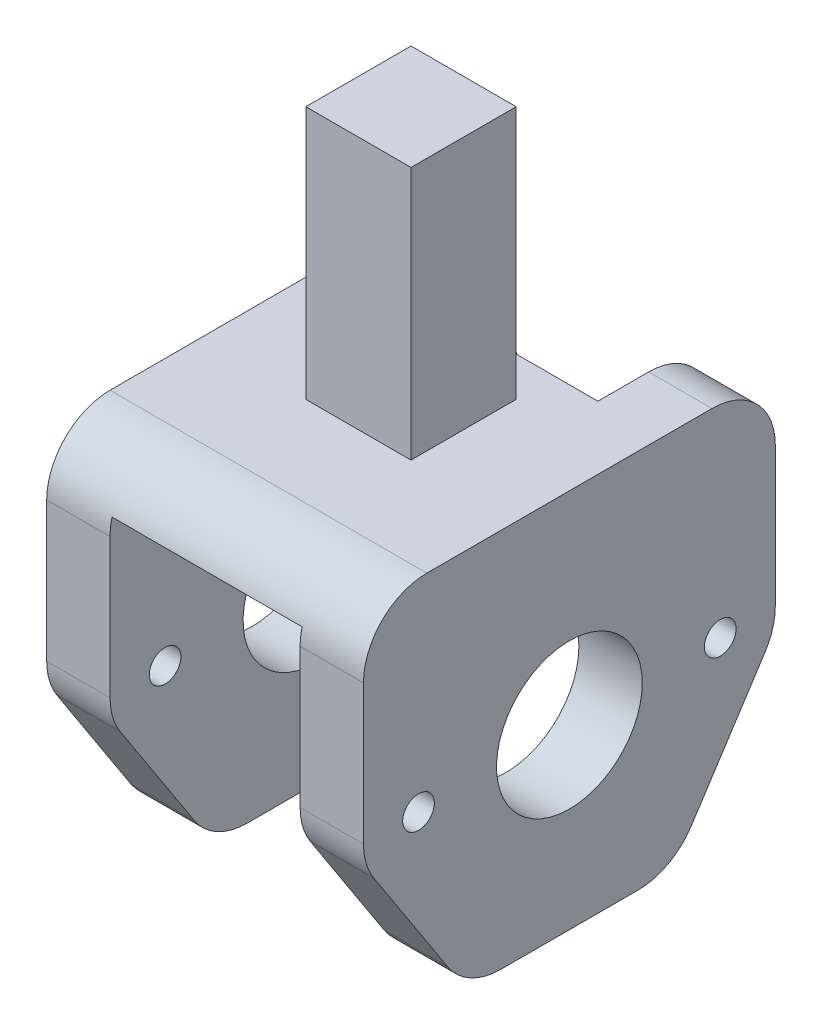
SolidWorks part; units mm, degrees
material "Nylon - impressão"
ref_plane "Plano frontal" through (0, 0, 0) normal (0, 0, 1) x (1, 0, 0)
ref_plane "Plano superior" through (0, 0, 0) normal (0, 1, 0) x (1, 0, 0)
ref_plane "Plano direito" through (0, 0, 0) normal (1, 0, 0) x (0, 0, -1)
sketch "Esboço1" plane through (0, 0, 0) normal (0, 1, 0) x (1, 0, 0)
  line L1 (-8.3, -8.3) -> (8.3, -8.3)
  line L2 (-8.3, -8.3) -> (-8.3, 8.3)
  line L3 (-8.3, 8.3) -> (8.3, 8.3)
  line L4 (8.3, -8.3) -> (8.3, 8.3)
  line L5 (-8.3, -8.3) -> (8.3, 8.3) construction
  line L6 (-8.3, 8.3) -> (8.3, -8.3) construction
  point P0 (0, 0)
  dimension "D1" = 16.6
extrude "Ressalto-extrusão1" add sketch "Esboço1" along normal blind 40
sketch "Esboço2" plane through (0, 0, 0) normal (0, -1, 0) x (1, 0, 0)
  line L1 (-25, -32.5) -> (25, -32.5)
  line L2 (-25, -32.5) -> (-25, 32.5)
  line L3 (-25, 32.5) -> (25, 32.5)
  line L4 (25, -32.5) -> (25, 32.5)
  line L5 (-25, -32.5) -> (25, 32.5) construction
  line L6 (-25, 32.5) -> (25, -32.5) construction
  point P0 (0, 0)
  dimension "D1" = 65
  dimension "D2" = 50
extrude "Ressalto-extrusão2" add sketch "Esboço2" along normal blind 60
sketch "Esboço3" plane through (0, 0, 32.5) normal (0, 0, 1) x (1, 0, 0)
  line L0 (25, -60) -> (-25, -60) construction
  line L1 (-15, -60) -> (15, -60)
  line L2 (-15, -60) -> (-15, -7.5)
  line L3 (-15, -7.5) -> (15, -7.5)
  line L4 (15, -60) -> (15, -7.5)
  line L5 (-25, -60) -> (-25, 0) construction
  line L6 (25, 0) -> (-25, 0) construction
  line L7 (25, -60) -> (25, 0) construction
  dimension "D1" = 10
  dimension "D2" = 7.5
  dimension "D3" = 10
extrude "Corte-extrusão1" cut sketch "Esboço3" against normal through all
sketch "Esboço4" plane through (25, 0, 0) normal (1, 0, 0) x (0, 0, -1)
  line L0 (32.5, -60) -> (-32.5, -60) construction
  line L1 (32.5, -60) -> (32.5, 0) construction
  circle A3 centre (0, -32) radius 11.5
  circle A10 centre (-23.8125, -32) radius 2.5
  circle A13 centre (23.8125, -32) radius 2.5
  circle A16 centre (0, -32) radius 23.8125 construction
  arc A17 (-9.4071, -11.4434) -> (-11.8406, -13.8769) centre (-11.9062, -11.3778) ccw [skipped]
  arc A18 (11.8464, -13.8771) -> (13.5071, -13.298) centre (11.9063, -11.3778) ccw [skipped]
  arc A20 (-11.8406, -55.1214) -> (-14.4054, -52.5566) centre (-11.9062, -52.6222) ccw [skipped]
  arc A21 (11.8345, -55.1212) -> (10.2346, -54.4811) centre (11.9063, -52.6222) ccw [skipped]
  point P9 (23.8125, -32)
  point P21 (0, -32)
  point P22 (0, -32)
  dimension "D2" = 47.625
  dimension "D4" = 5
  dimension "D5" = 23
  dimension "D1" = 28
  dimension "D3" = 32.5
  dimension "D6" = 6
extrude "Corte-extrusão2" cut sketch "Esboço4" against normal through all
sketch "Esboço5" plane through (-25, 0, 0) normal (-1, 0, 0) x (0, 0, 1)
  line L0 (0, 0) -> (0, -9.2798) construction
  line L1 (32.5, 0) -> (-32.5, 0) construction
  line L3 (-14.5, -11) -> (-14.5, 0)
  line L4 (-14.5, 0) -> (-32.5, 0)
  line L5 (-32.5, 0) -> (-32.5, -11)
  line L6 (-32.5, -60) -> (-32.5, 0) construction
  line L7 (-32.5, -11) -> (-14.5, -11)
  dimension "D1" = 18
  dimension "D2" = 11
extrude "Corte-extrusão3" cut sketch "Esboço5" against normal blind 40
chamfer "Chanfro1" distance 25 angle 33 4 edges at (-20, -60, -32.5) (-20, -60, 32.5) (20, -60, 32.5) (20, -60, -32.5) first distance on face at (-20, -35.5, -32.5) first distance on face at (0, -31.875, 32.5) first distance on face at (20, -30, -32.5)
fillet "Filete2" radius 10 11 edges at (20, 0, -32.5) (20, -35, -32.5) (20, -60, 16.2648) (20, -60, -16.2648) (20, -35, 32.5) (0, 0, 32.5) (-20, -60, -16.2648) (-20, -60, 16.2648) (-20, -35, 32.5) (-20, -35, -32.5) (-20, -11, -32.5)
